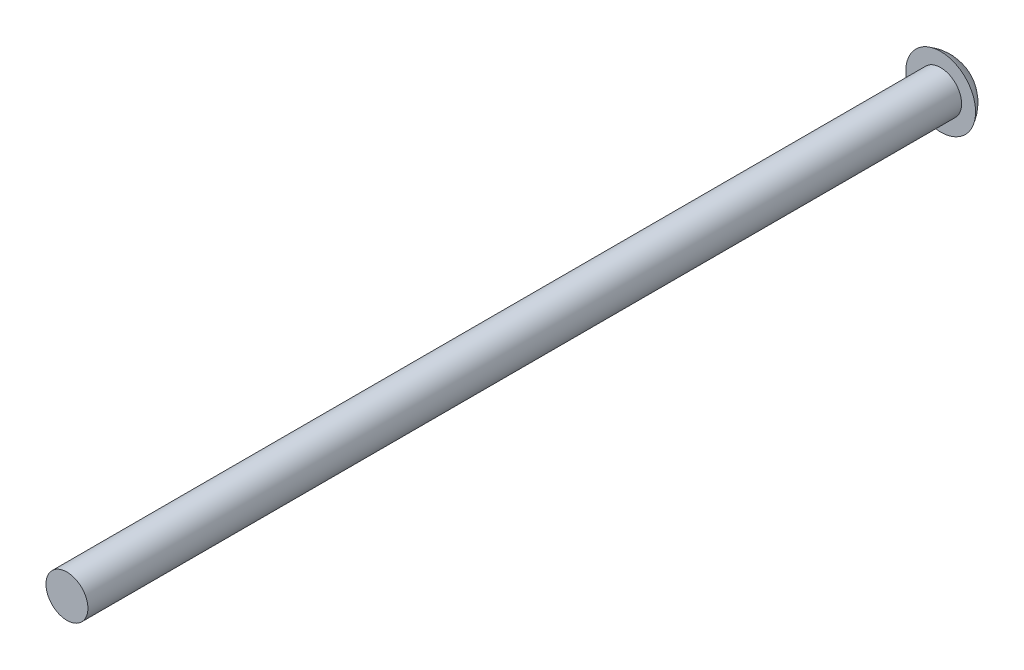
SolidWorks part; units mm, degrees
material "镀铬不锈钢"
ref_plane "前视基准面" through (0, 0, 0) normal (0, 0, 1) x (1, 0, 0)
ref_plane "上视基准面" through (0, 0, 0) normal (0, 1, 0) x (1, 0, 0)
ref_plane "右视基准面" through (0, 0, 0) normal (1, 0, 0) x (0, 0, -1)
sketch "草图1" plane through (0, 0, 0) normal (0, 0, 1) x (1, 0, 0)
  circle A0 centre (0, 0) radius 3
  dimension "D1" = 6
extrude "凸台-拉伸1" add sketch "草图1" along normal blind 125
sketch "草图2" plane through (0, 0, 0) normal (0, 1, 0) x (1, 0, 0)
  line L0 (0, 0) -> (5, 0)
  line L1 (0, 0) -> (0, 3)
  arc A0 (0, 3) -> (5, 0) centre (0, -2.6667) cw
  dimension "D1" = 5
  dimension "D2" = 3
revolve "旋转1" add sketch "草图2" angle 360 about L1
